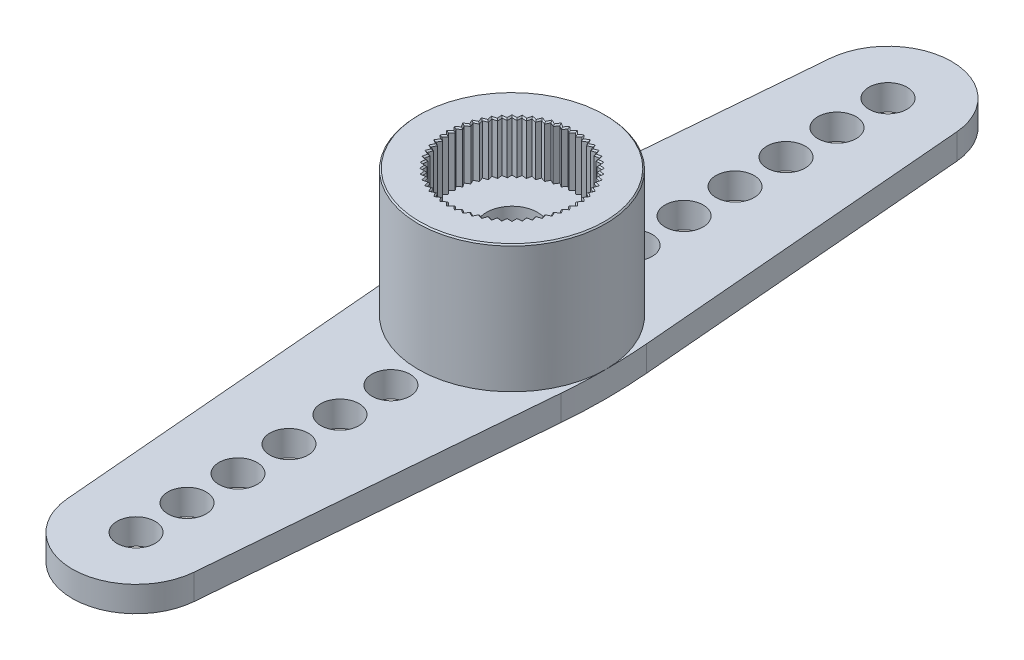
SolidWorks part; units mm, degrees
note: The reader was unsure of these and kept them because the rebuilt part matched: shared geometry of "草图1<4>".
ref_plane "前视基准面" through (0, 0, 0) normal (0, 0, 1) x (1, 0, 0)
ref_plane "上视基准面" through (0, 0, 0) normal (0, 1, 0) x (1, 0, 0)
ref_plane "右视基准面" through (0, 0, 0) normal (1, 0, 0) x (0, 0, -1)
sketch "草图1" plane through (0, 0, 0) normal (0, 1, 0) x (1, 0, 0)
  line L0 (0, -14.75) -> (0, 14.75) construction
  line L1 (-2.5, -14.75) -> (-2.5, 14.75) construction
  line L2 (2.5, -14.75) -> (2.5, 14.75) construction
  line L3 (-3.6089, 1.677) -> (-2.3893, 16.1708)
  line L4 (-3.6089, -1.677) -> (-2.3675, -16.4292)
  line L5 (0, -14.75) -> (0, -27.3889) construction
  line L6 (3.6089, 1.677) -> (2.3893, 16.1708)
  line L7 (3.6089, -1.677) -> (2.3675, -16.4292)
  line L8 (0, 0) -> (-21.5095, 0) construction
  arc A0 (-2.5, -14.75) -> (2.5, -14.75) centre (0, -14.75) ccw construction
  arc A1 (2.5, 14.75) -> (-2.5, 14.75) centre (0, 14.75) ccw construction
  circle A2 centre (0, 14.75) radius 0.75
  arc A4 (3.6089, 1.677) -> (3.6089, -1.677) centre (-16.3207, 0) cw
  arc A5 (-3.6089, 1.677) -> (-3.6089, -1.677) centre (16.3207, 0) ccw
  circle A6 centre (0, 0) radius 3.6793 construction
  circle A7 centre (0, 12.75) radius 0.75
  circle A8 centre (0, 10.75) radius 0.75
  circle A9 centre (0, 8.75) radius 0.75
  circle A10 centre (0, 6.75) radius 0.75
  circle A11 centre (0, 4.75) radius 0.75
  arc A12 (-2.5, 14.75) -> (2.5, 14.75) centre (0, 14.75) cw
  arc A13 (-2.5, -14.75) -> (2.5, -14.75) centre (0, -14.75) ccw
  circle A14 centre (0, -14.75) radius 0.75
  circle A15 centre (0, -12.75) radius 0.75
  circle A16 centre (0, -10.75) radius 0.75
  circle A17 centre (0, -8.75) radius 0.75
  circle A18 centre (0, -6.75) radius 0.75
  circle A19 centre (0, -4.75) radius 0.75
  circle A20 centre (0, 0) radius 1
  point P2 (0, 0)
  point P20 (3.75, 0)
  point P23 (-3.75, 0)
  dimension "D2" = 2.5
  dimension "D3" = 1.5
  dimension "D4" = 3.75
  dimension "D5" = 20
  dimension "D8" = 2
  dimension "D1" = 29.5
  dimension "D7" = 2
  dimension "D6" = 6
extrude "凸台-拉伸1" add sketch "草图1" along normal blind 1
sketch "草图2" plane through (0, 1, 0) normal (0, 1, 0) x (1, 0, 0)
  circle A0 centre (0, 0) radius 3.6793 construction
  circle A1 centre (0, 0) radius 3.6793
  circle A2 centre (0, 0) radius 1.5
  dimension "D1" = 3
extrude "凸台-拉伸2" add sketch "草图2" along normal blind 5 contours A1
extrude "切除-拉伸2" cut sketch "草图1<4>" along normal through all contours A20
sketch "草图1<4>" plane through (0, 0, 0) normal (0, 1, 0) x (1, 0, 0) same geometry as "草图1"
sketch "草图3" plane through (0, 6, 0) normal (0, 1, 0) x (1, 0, 0)
  circle A0 centre (0, 0) radius 2.355
  dimension "D1" = 4.71
extrude "切除-拉伸3" cut sketch "草图3" against normal blind 2
sketch "草图4" plane through (0, 6, 0) normal (0, 1, 0) x (1, 0, 0)
  line L0 (0, 0) -> (0, 5.1126) construction
  line L1 (0, 3.818) -> (-0.1414, 3.6766)
  line L2 (0, 3.818) -> (0.1414, 3.6766)
  arc A0 (3.6793, 0) -> (-3.6793, 0) centre (0, 0) ccw construction
  arc A1 (3.6793, 0) -> (-3.6793, 0) centre (0, 0) ccw construction
  arc A2 (-0.1414, 3.6766) -> (0.1414, 3.6766) centre (0, 0) cw
  dimension "D1" = 90
  dimension "D2" = 0.2
sketch "草图5" plane through (0, 4, 0) normal (0, 1, 0) x (1, 0, 0)
  line L0 (0, 2.4922) -> (0.1414, 2.3507)
  line L1 (0, 0) -> (0, 5.1126) construction
  line L2 (0, 2.4922) -> (-0.1414, 2.3507)
  circle A1 centre (0, 0) radius 2.355 construction
  circle A2 centre (0, 0) radius 2.355 construction
  arc A3 (-0.1414, 2.3507) -> (0.1414, 2.3507) centre (0, 0) cw
  dimension "D1" = 90
  dimension "D2" = 0.2
extrude "切除-拉伸4" cut sketch "草图5" along normal up to next
pattern_circular "阵列(圆周)1" count 56 over 360 about axis through (0, 0, 0) along (0, 1, 0) of "切除-拉伸4"
chamfer "倒角1" distance 0.05 angle 45 113 edges at (-0.4752, 6, -2.3798) (-0.6044, 6, -2.3503) (-0.7387, 6, -2.3117) (-0.8638, 6, -2.2679) (-0.9929, 6, -2.2144) (-1.1123, 6, -2.1569) (-1.2346, 6, -2.0893) (-1.3468, 6, -2.0188) (-1.4607, 6, -1.938) (-1.5643, 6, -1.8553) (-1.6685, 6, -1.7622) (-1.7622, 6, -1.6685) (-1.8553, 6, -1.5643) (-1.938, 6, -1.4607) (-2.0188, 6, -1.3468) (-2.0893, 6, -1.2346) (-2.1569, 6, -1.1123) (-2.2144, 6, -0.9929) (-2.2679, 6, -0.8638) (-2.3117, 6, -0.7387) (-2.3503, 6, -0.6044) (-2.3798, 6, -0.4752) (-2.4032, 6, -0.3375) (-2.4181, 6, -0.2058) (-2.4259, 6, -0.0663) (-2.4259, 6, 0.0663) (-2.4181, 6, 0.2058) (-2.4032, 6, 0.3375) (-2.3798, 6, 0.4752) (-2.3503, 6, 0.6044) (-2.3117, 6, 0.7387) (-2.2679, 6, 0.8638) (-2.2144, 6, 0.9929) (-2.1569, 6, 1.1123) (-2.0893, 6, 1.2346) (-2.0188, 6, 1.3468) (-1.938, 6, 1.4607) (-1.8553, 6, 1.5643) (-1.7622, 6, 1.6685) (-1.6685, 6, 1.7622) (-1.5643, 6, 1.8553) (-1.4607, 6, 1.938) (-1.3468, 6, 2.0188) (-1.2346, 6, 2.0893) (-1.1123, 6, 2.1569) (-0.9929, 6, 2.2144) (-0.8638, 6, 2.2679) (-0.7387, 6, 2.3117) (-0.6044, 6, 2.3503) (-0.4752, 6, 2.3798) (-0.3375, 6, 2.4032) (-0.2058, 6, 2.4181) (-0.0663, 6, 2.4259) (0.0663, 6, 2.4259) (0.2058, 6, 2.4181) (0.3375, 6, 2.4032) (0.4752, 6, 2.3798) (0.6044, 6, 2.3503) (0.7387, 6, 2.3117) (0.8638, 6, 2.2679) (0.9929, 6, 2.2144) (1.1123, 6, 2.1569) (1.2346, 6, 2.0893) (1.3468, 6, 2.0188) (1.4607, 6, 1.938) (1.5643, 6, 1.8553) (1.6685, 6, 1.7622) (1.7622, 6, 1.6685) (1.8553, 6, 1.5643) (1.938, 6, 1.4607) (2.0188, 6, 1.3468) (2.0893, 6, 1.2346) (2.1569, 6, 1.1123) (2.2144, 6, 0.9929) (2.2679, 6, 0.8638) (2.3117, 6, 0.7387) (2.3503, 6, 0.6044) (2.3798, 6, 0.4752) (2.4032, 6, 0.3375) (2.4181, 6, 0.2058) (2.4259, 6, 0.0663) (2.4259, 6, -0.0663) (2.4181, 6, -0.2058) (2.4032, 6, -0.3375) (2.3798, 6, -0.4752) (2.3503, 6, -0.6044) (2.3117, 6, -0.7387) (2.2679, 6, -0.8638) (2.2144, 6, -0.9929) (2.1569, 6, -1.1123) (2.0893, 6, -1.2346) (2.0188, 6, -1.3468) (1.938, 6, -1.4607) (1.8553, 6, -1.5643) (1.7622, 6, -1.6685) (1.6685, 6, -1.7622) (1.5643, 6, -1.8553) (1.4607, 6, -1.938) (1.3468, 6, -2.0188) (1.2346, 6, -2.0893) (1.1123, 6, -2.1569) (0.9929, 6, -2.2144) (0.8638, 6, -2.2679) (0.7387, 6, -2.3117) (0.6044, 6, -2.3503) (0.4752, 6, -2.3798) (0.3375, 6, -2.4032) (0.2058, 6, -2.4181) (0.0663, 6, -2.4259) (-0.0663, 6, -2.4259) (-0.2058, 6, -2.4181) (-0.3375, 6, -2.4032) (0, 6, 3.6793)
